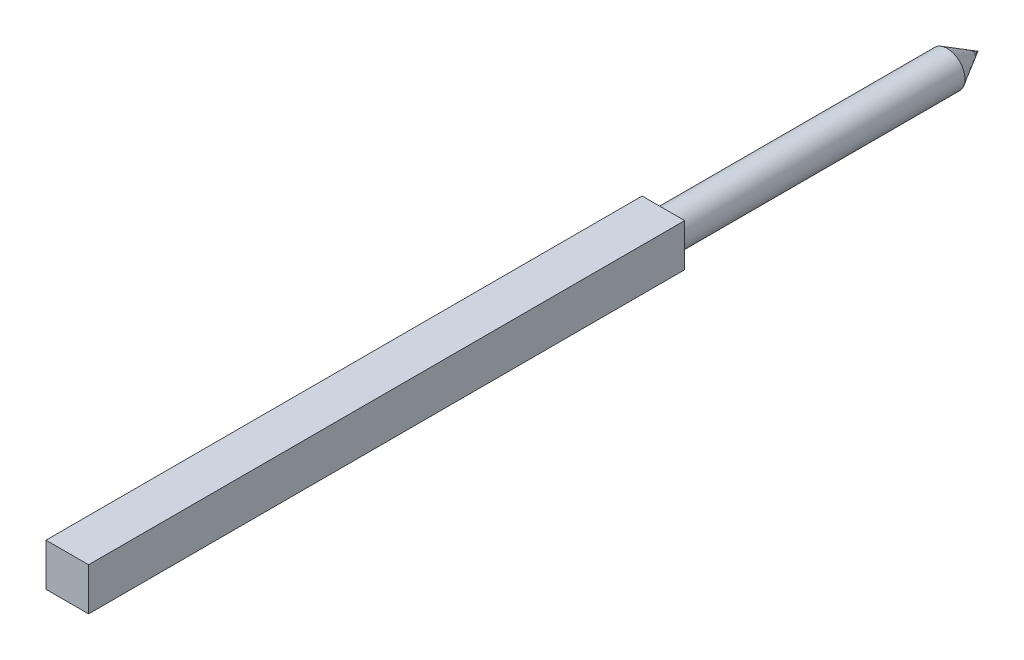
SolidWorks part; units mm, degrees
ref_plane "Front Plane" through (0, 0, 0) normal (0, 0, 1) x (1, 0, 0)
ref_plane "Top Plane" through (0, 0, 0) normal (0, 1, 0) x (1, 0, 0)
ref_plane "Right Plane" through (0, 0, 0) normal (1, 0, 0) x (0, 0, -1)
sketch "Sketch1" plane through (0, 0, 0) normal (0, 0, 1) x (1, 0, 0)
  line L1 (-3, -3) -> (3, -3)
  line L2 (-3, -3) -> (-3, 3)
  line L3 (-3, 3) -> (3, 3)
  line L4 (3, -3) -> (3, 3)
  line L5 (-3, -3) -> (3, 3) construction
  line L6 (-3, 3) -> (3, -3) construction
  circle A0 centre (0, 0) radius 2.5
  point P0 (0, 0)
  point P8 (0, 0)
  dimension "D3" = 5
  dimension "D1" = 6
  dimension "D2" = 6
extrude "Boss-Extrude1" add sketch "Sketch1" along normal blind 84 contours L2 L3 L4 L1
extrude "Boss-Extrude2" add sketch "Sketch1<4>" against normal blind 40 contours A0
sketch "Sketch1<4>" plane through (0, 0, 0) normal (0, 0, 1) x (1, 0, 0) same geometry as "Sketch1"
sketch "Sketch6" plane through (0, 0, -40) normal (0, 0, -1) x (-1, 0, 0)
  circle A0 centre (0, 0) radius 2.5 construction
  circle A1 centre (0, 0) radius 2.5
extrude "Boss-Extrude3" add sketch "Sketch6" along normal blind 40 draft 30
